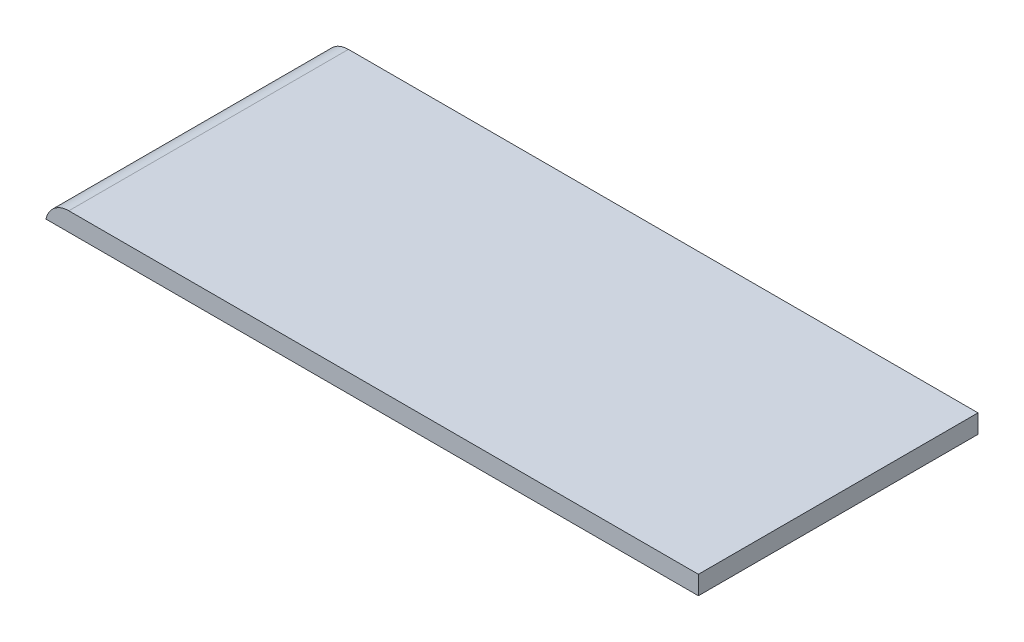
SolidWorks part; units mm, degrees
material "ABS"
ref_plane "Спереди" through (0, 0, 0) normal (0, 0, 1) x (1, 0, 0)
ref_plane "Сверху" through (0, 0, 0) normal (0, 1, 0) x (1, 0, 0)
ref_plane "Справа" through (0, 0, 0) normal (1, 0, 0) x (0, 0, -1)
sketch "Эскиз1" plane through (0, 0, 0) normal (0, 1, 0) x (1, 0, 0)
  line L1 (-80.6067, -49.4978) -> (-10.6067, -49.4978)
  line L2 (-80.6067, -49.4978) -> (-80.6067, -19.4978)
  line L3 (-80.6067, -19.4978) -> (-10.6067, -19.4978)
  line L4 (-10.6067, -49.4978) -> (-10.6067, -19.4978)
extrude "Бобышка-Вытянуть1" add sketch "Эскиз1" along normal blind 2
fillet "Скругление1" radius 2.5 1 edges at (-80.6067, 2, 34.4978)
